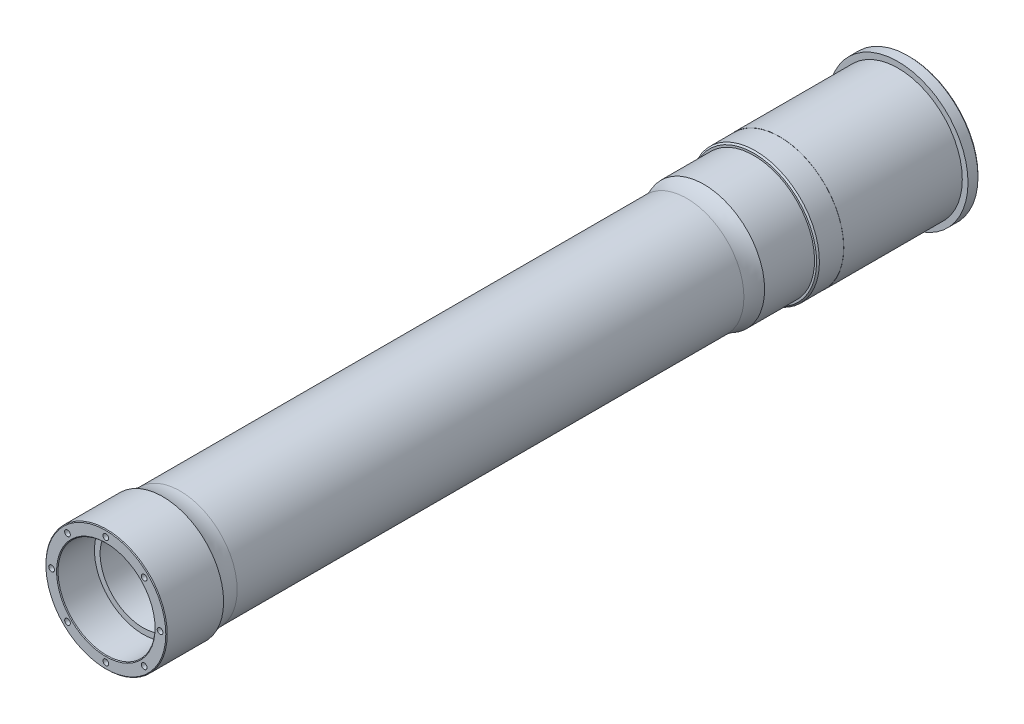
SolidWorks part; units mm, degrees
ref_plane "前视基准面" through (0, 0, 0) normal (0, 0, 1) x (1, 0, 0)
ref_plane "上视基准面" through (0, 0, 0) normal (0, 1, 0) x (1, 0, 0)
ref_plane "右视基准面" through (0, 0, 0) normal (1, 0, 0) x (0, 0, -1)
sketch "草图1" plane through (0, 0, 0) normal (0, 0, 1) x (1, 0, 0)
  circle A0 centre (0, 0) radius 37.5
  circle A1 centre (0, 0) radius 34
  dimension "D1" = 75
  dimension "D2" = 68
extrude "拉伸1" add sketch "草图1" along normal blind 600
sketch "草图2" plane through (0, 0, 600) normal (0, 0, 1) x (1, 0, 0)
  circle A0 centre (0, 0) radius 49
  circle A1 centre (0, 0) radius 22.5
  dimension "D1" = 98
extrude "拉伸2" add sketch "草图2" against normal blind 563
sketch "草图3" plane through (0, 0, 600) normal (0, 0, 1) x (1, 0, 0)
  circle A0 centre (0, 0) radius 50
  circle A1 centre (0, 0) radius 45
  dimension "D1" = 100
  dimension "D2" = 90
extrude "切除-拉伸1" cut sketch "草图3" against normal blind 555
sketch "草图4" plane through (0, 0, 600) normal (0, 0, 1) x (1, 0, 0)
  circle A0 centre (0, 0) radius 47.5
  circle A1 centre (0, 0) radius 44.9
  dimension "D1" = 95
  dimension "D2" = 89.8
extrude "切除-拉伸2" cut sketch "草图4" against normal blind 472
sketch "草图5" plane through (0, 0, 600) normal (0, 0, 1) x (1, 0, 0)
  circle A0 centre (0, 0) radius 45
  circle A1 centre (0, 0) radius 40
  dimension "D1" = 90
  dimension "D2" = 80
extrude "切除-拉伸3" cut sketch "草图5" against normal blind 454
sketch "草图6" plane through (0, 0, 0) normal (0, 0, -1) x (-1, 0, 0)
  circle A0 centre (0, 0) radius 34
  dimension "D1" = 68
extrude "切除-拉伸4" cut sketch "草图6" against normal blind 63
sketch "草图7" plane through (0, 0, 600) normal (0, 0, 1) x (1, 0, 0)
  circle A0 centre (0, 0) radius 30
  dimension "D1" = 60
extrude "切除-拉伸5" cut sketch "草图7" against normal through all
chamfer "倒角1" distance 1 angle 45 1 edges at (49, 0, 37)
sketch "草图11" plane through (0, 0, 0) normal (0, 0, -1) x (-1, 0, 0)
  circle A0 centre (0, 0) radius 37.5
extrude "切除-拉伸6" cut sketch "草图11" against normal blind 37
sketch "草图12" plane through (0, 0, 600) normal (0, 0, 1) x (1, 0, 0)
sketch "草图13" plane through (0, 0, 600) normal (0, 0, 1) x (1, 0, 0)
  circle A0 centre (0, 0) radius 34
  dimension "D1" = 68
extrude "切除-拉伸7" cut sketch "草图13" against normal blind 26
sketch "草图15" plane through (0, 0, 600) normal (0, 0, 1) x (1, 0, 0)
  circle A0 centre (0, 0) radius 42.5
  circle A1 centre (0, 0) radius 40
  dimension "D1" = 85
extrude "拉伸3" add sketch "草图15" against normal blind 40
sketch "草图16" plane through (0, 0, 600) normal (0, 0, 1) x (1, 0, 0)
  circle A0 centre (26.8701, 26.8701) radius 2
  circle A1 centre (0, 38) radius 2
  circle A2 centre (38, 0) radius 2
  circle A3 centre (26.8701, -26.8701) radius 2
  circle A4 centre (0, -38) radius 2
  circle A5 centre (-26.8701, -26.8701) radius 2
  circle A6 centre (-38, 0) radius 2
  circle A7 centre (-26.8701, 26.8701) radius 2
  dimension "D1" = 4
extrude "切除-拉伸9" cut sketch "草图16" against normal blind 15
fillet "圆角1" radius 30 1 edges at (40, 0, 560)
sketch "草图17" plane through (0, 0, 146) normal (0, 0, 1) x (1, 0, 0)
  circle A0 centre (0, 0) radius 40
  circle A1 centre (0, 0) radius 42.5
extrude "拉伸4" add sketch "草图17" along normal blind 35
chamfer "倒角2" distance 0.5 angle 45 2 edges at (34, 0, 600) (42.5, 0, 600)
fillet "圆角2" radius 30 1 edges at (40, 0, 181)
chamfer "倒角3" distance 1 angle 45 1 edges at (44.9, 0, 146)
sketch "草图19" plane through (0, 0, 37) normal (0, 0, -1) x (-1, 0, 0)
  circle A1 centre (0, 38) radius 2
  circle A2 centre (26.8701, 26.8701) radius 2
  circle A3 centre (38, 0) radius 2
  circle A4 centre (26.8701, -26.8701) radius 2
  circle A5 centre (0, -38) radius 2
  circle A6 centre (-26.8701, -26.8701) radius 2
  circle A7 centre (-38, 0) radius 2
  circle A8 centre (-26.8701, 26.8701) radius 2
  dimension "D1" = 4
extrude "切除-拉伸10" cut sketch "草图19" against normal blind 15
chamfer "倒角4" distance 0.5 angle 45 1 edges at (-34, 0, 37)
ref_plane "基准面1" through (0, -44.9, 0) normal (0, 1, 0) x (-1, 0, 0)
sketch "草图20" plane through (0, -44.9, 0) normal (0, 1, 0) x (-1, 0, 0)
  line L0 (45, 128) -> (-45, 128) construction
  line L1 (-2.5, 130.5) -> (-2.5, 146)
  line L2 (43.9, 146) -> (-43.9, 146) construction
  line L3 (-2.5, 146) -> (2.5, 146)
  line L4 (2.5, 146) -> (2.5, 130.5)
  arc A0 (-2.5, 130.5) -> (2.5, 130.5) centre (0, 130.5) ccw
  dimension "D1" = 5
  dimension "D3" = 2.5
extrude "切除-拉伸11" cut sketch "草图20" along normal blind 2.4
